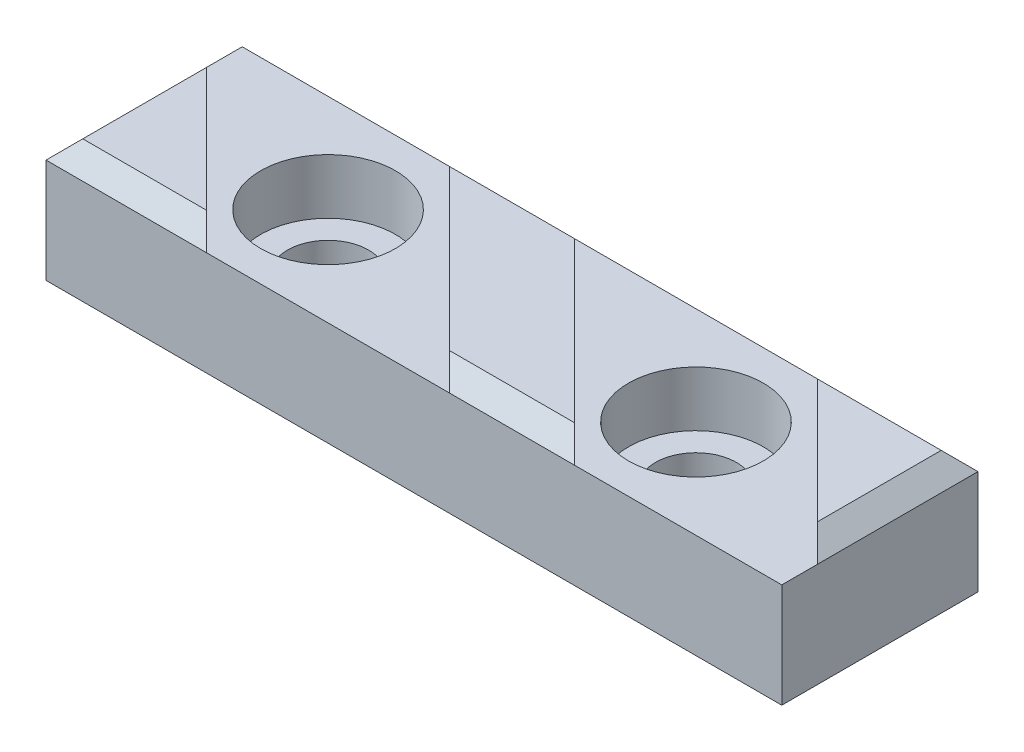
SolidWorks part; units mm, degrees
material "AISI 304"
ref_plane "前视基准面" through (0, 0, 0) normal (0, 0, 1) x (1, 0, 0)
ref_plane "上视基准面" through (0, 0, 0) normal (0, 1, 0) x (1, 0, 0)
ref_plane "右视基准面" through (0, 0, 0) normal (1, 0, 0) x (0, 0, -1)
sketch "草图1" plane through (0, 0, 0) normal (0, 1, 0) x (1, 0, 0)
  line L1 (0, 0) -> (60, 0)
  line L2 (0, 0) -> (0, 16)
  line L3 (0, 16) -> (60, 16)
  line L4 (60, 0) -> (60, 16)
  dimension "D1" = 16
  dimension "D2" = 60
extrude "凸台-拉伸1" add sketch "草图1" along normal blind 8.5
sketch "草图2" plane through (0, 8.5, 0) normal (0, 1, 0) x (1, 0, 0)
  line L0 (0, 0) -> (60, 0) construction
  line L1 (60, 0) -> (60, 16) construction
  line L2 (60, 16) -> (0, 16) construction
  line L3 (0, 16) -> (0, 0) construction
  line L4 (0, 0) -> (60, 0)
  line L5 (60, 0) -> (60, 16)
  line L6 (60, 16) -> (0, 16)
  line L7 (0, 16) -> (0, 0)
  line L8 (0, 13.1005) -> (13.1005, 0)
  line L9 (32.8995, 0) -> (16.8995, 16)
  line L10 (27.1005, 16) -> (43.1005, 0)
  line L11 (60, 2.8995) -> (46.8995, 16)
  line L12 (15, 16) -> (15, 0) construction
  line L13 (0, 8) -> (60, 8) construction
  line L15 (45, 17.7416) -> (45, 0) construction
  circle A0 centre (15, 8) radius 5.5
  circle A2 centre (45, 8) radius 5.5
  line M6 (0, 0) -> (60, 0)
  line M8 (60, 16) -> (0, 16)
  dimension "D2" = 11
  dimension "D7" = 11
  dimension "D3" = 14
  dimension "D4" = 14
  dimension "D5" = 45
  dimension "D6" = 8
  dimension "D8" = 7
  dimension "D9" = 15
  dimension "D10" = 15
  dimension "D11" = 7
extrude "切除-拉伸1" cut sketch "草图2" against normal blind 4.5 contours A0 | A2
extrude "凸台-拉伸2" add sketch "草图2<3>" along normal blind 1.5 contours L8 L7 M6 | L10 L6 L9 M6 | L11 L5 M8 region at (4.3668, 8.5, -4.3668) region at (30, 8.5, -8) region at (55.6332, 8.5, -11.6332)
sketch "草图2<3>" plane through (0, 8.5, 0) normal (0, 1, 0) x (1, 0, 0) same geometry as "草图2"
sketch "草图3" plane through (0, 4, 0) normal (0, 1, 0) x (1, 0, 0)
  circle A0 centre (15, 8) radius 3.3
  circle A1 centre (45, 8) radius 3.3
  dimension "D1" = 6.6
  dimension "D2" = 6.6
extrude "切除-拉伸2" cut sketch "草图3" against normal through all
chamfer "倒角1" distance 1.5 angle 45 6 edges at (6.5503, 10, 0) (0, 10, -6.5503) (22, 10, -16) (38, 10, 0) (60, 10, -9.4497) (53.4497, 10, -16)
